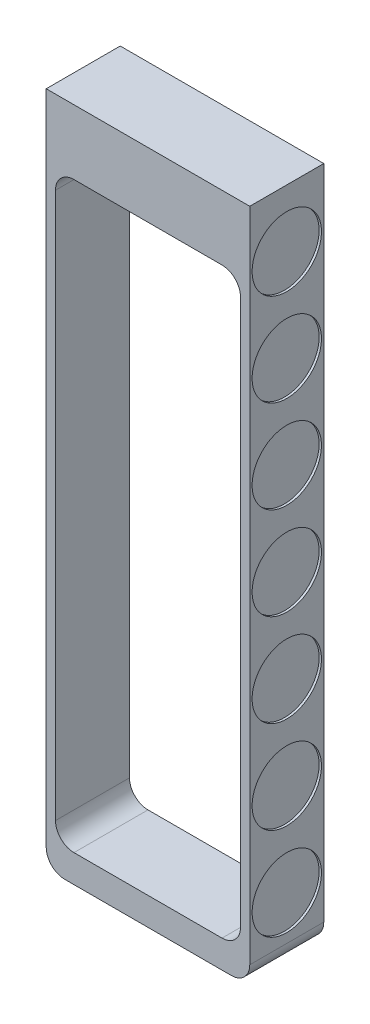
SolidWorks part; units mm, degrees
material "Сплав 2024"
ref_plane "Спереди" through (0, 0, 0) normal (0, 0, 1) x (1, 0, 0)
ref_plane "Сверху" through (0, 0, 0) normal (0, 1, 0) x (1, 0, 0)
ref_plane "Справа" through (0, 0, 0) normal (1, 0, 0) x (0, 0, -1)
sketch "Эскиз1" plane through (0, 0, 0) normal (0, 0, 1) x (1, 0, 0)
  line L1 (0, 0) -> (44, 0)
  line L2 (0, 0) -> (0, 146)
  line L3 (0, 146) -> (44, 146)
  line L4 (44, 0) -> (44, 146)
  dimension "D1" = 44
  dimension "D2" = 146
extrude "Бобышка-Вытянуть1" add sketch "Эскиз1" along normal blind 16
sketch "Эскиз2" plane through (0, 0, 16) normal (0, 0, 1) x (1, 0, 0)
  line L0 (22, 146) -> (22, 0) construction
  line L1 (44, 146) -> (0, 146) construction
  line L2 (0, 0) -> (44, 0) construction
  line L4 (2, 132) -> (42, 132)
  line L5 (2, 132) -> (2, 6)
  line L6 (2, 6) -> (42, 6)
  line L7 (42, 132) -> (42, 6)
  line L8 (2, 132) -> (42, 6) construction
  line L9 (2, 6) -> (42, 132) construction
  point P6 (22, 69)
  dimension "D1" = 40
  dimension "D2" = 126
  dimension "D3" = 6
extrude "Вырез-Вытянуть1" cut sketch "Эскиз2" against normal through all
fillet "Скругление1" radius 4 2 edges at (44, 0, 8) (0, 0, 8)
fillet "Скругление2" radius 4 4 edges at (42, 132, 8) (2, 132, 8) (42, 6, 8) (2, 6, 8)
sketch "Эскиз3" plane through (0, 0, 0) normal (-1, 0, 0) x (0, 0, 1)
  line L0 (8, 146) -> (8, 4) construction
  line L1 (16, 146) -> (0, 146) construction
  line L2 (0, 4) -> (16, 4) construction
  circle A0 centre (8, 133.5204) radius 7.5
  circle A1 centre (8, 113.5204) radius 7.5
  circle A2 centre (8, 93.5204) radius 7.5
  circle A3 centre (8, 73.5204) radius 7.5
  circle A4 centre (8, 53.5204) radius 7.5
  circle A5 centre (8, 33.5204) radius 7.5
  circle A6 centre (8, 13.5204) radius 7.5
  dimension "D1" = 15
  dimension "D2" = 7
extrude "Вырез-Вытянуть2" cut sketch "Эскиз3" against normal blind 0.5
ref_plane "Плоскость1" through (22, 0, 0) normal (1, 0, 0) x (0, 0, -1)
mirror "Зеркальное отражение1" about plane through (22, 0, 0) normal (1, 0, 0) of "Вырез-Вытянуть2"
